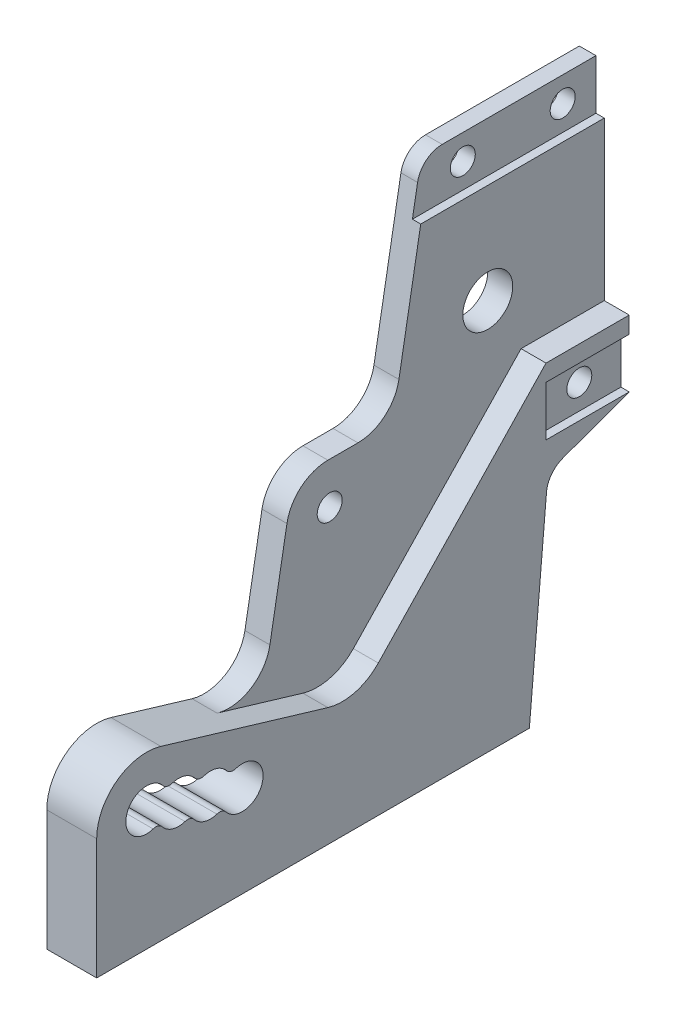
SolidWorks part; units mm, degrees
material "1060 Alloy"
ref_plane "Front Plane" through (0, 0, 0) normal (0, 0, 1) x (1, 0, 0)
ref_plane "Top Plane" through (0, 0, 0) normal (0, 1, 0) x (1, 0, 0)
ref_plane "Right Plane" through (0, 0, 0) normal (1, 0, 0) x (0, 0, -1)
sketch "Sketch1" plane through (0, 0, 0) normal (1, 0, 0) x (0, 0, -1)
  line L1 (0, 0) -> (64, 0)
  line L2 (0, 0) -> (0, 62)
  line L3 (0, 62) -> (64, 62)
  line L4 (64, 0) -> (64, 62)
  circle A0 centre (6, 14.5) radius 2.5
  circle A1 centre (50, 44) radius 3
  dimension "D1" = 6
  dimension "D2" = 5
  dimension "D3" = 14.5
  dimension "D4" = 6
  dimension "D5" = 44
  dimension "D6" = 50
  dimension "D7" = 64
  dimension "D8" = 62
extrude "Boss-Extrude1" add sketch "Sketch1" along normal blind 6
sketch "Sketch3" plane through (6, 0, 0) normal (1, 0, 0) x (0, 0, -1)
  line L57 (64, 0) -> (52, 0)
  line L58 (64, 0) -> (64, 29)
  line L59 (64, 29) -> (54.2259, 25.4425)
  line L60 (52, 0) -> (54.2259, 25.4425)
  dimension "D1" = 70
  dimension "D2" = 29
  dimension "D3" = 52
  dimension "D4" = 85
extrude "Cut-Extrude2" cut sketch "Sketch3" against normal up to next
fillet "Fillet2" radius 3 1 edges at (3, 25.4425, -54.2259)
hole_wizard "Tap Drill for M3 Tap1" positions "Sketch5" profile "Sketch4" hole size "M3" standard "ISO"
sketch "Sketch5" plane through (0, 0, 0) normal (0, -1, 0) x (-1, 0, 0)
  line L0 (0, 0) -> (0, 52) construction
  line L1 (-6, 0) -> (0, 0) construction
  point P0 (-3, 48)
  point P2 (-3, 12)
  dimension "D1" = 3
  dimension "D2" = 12
  dimension "D3" = 36
sketch "Sketch4" plane through (3, 0, -48) normal (1, 0, 0) x (0, 0, -1)
  line L0 (0, 0) -> (0, 9.7511)
  line L1 (0, 9.7511) -> (1.25, 9)
  line L2 (1.25, 9) -> (1.25, 0)
  line L5 (1.25, 0) -> (0, 0)
  line L10 (0, 9.7511) -> (-1.25, 9) construction
  line L11 (0, -6.35) -> (0, 107.95) construction
  dimension "Hole Dia." = 2.5
  dimension "Hole Depth" = 9
  dimension "Drill Angle" = 118
sketch "Sketch9" plane through (6, 0, 0) normal (1, 0, 0) x (0, 0, -1)
  line L0 (7.7183, 20.2487) -> (27.7834, 14.2513)
  line L1 (0, 0) -> (52, 0) construction
  line L19 (43, 62) -> (35.4106, 18.9581)
  line L21 (0, 62) -> (0, 0) construction
  line L22 (43, 62) -> (0, 62)
  line L23 (0, 62) -> (0, 14.5)
  line L24 (0, 62) -> (0, 0) construction
  line L25 (64, 62) -> (0, 62) construction
  arc A0 (35.4106, 18.9581) -> (27.7834, 14.2513) centre (29.5017, 20) cw
  arc A12 (0, 14.5) -> (7.7183, 20.2487) centre (6, 14.5) cw
  circle A16 centre (6, 14.5) radius 2.5 construction
  dimension "D1" = 43
  dimension "D2" = 80
  dimension "D3" = 20
extrude "Cut-Extrude3" cut sketch "Sketch9" against normal blind 8
sketch "Sketch13" plane through (6, 0, 0) normal (1, 0, 0) x (0, 0, -1)
  line L0 (64, 29) -> (64, 62) construction
  line L1 (54, 37) -> (64, 37)
  line L2 (64, 62) -> (43, 62) construction
  line L3 (64, 62) -> (42, 62)
  line L4 (64, 37) -> (64, 62)
  line L11 (42, 62) -> (33.8443, 15.8597)
  line L15 (33.8443, 15.8597) -> (54, 37)
  arc A0 (27.7834, 14.2513) -> (35.4106, 18.9581) centre (29.5017, 20) ccw construction
  dimension "D1" = 10
  dimension "D3" = 25
  dimension "D4" = 22
extrude "Cut-Extrude4" cut sketch "Sketch13" against normal blind 3
fillet "Fillet3" radius 3 1 edges at (1.5, 62, -43)
sketch "Sketch14" plane through (3, 0, 0) normal (1, 0, 0) x (0, 0, -1)
  line L0 (64, 37) -> (64, 62) construction
  line L1 (64, 62) -> (45.5173, 62) construction
  circle A0 centre (60, 59) radius 1.5
  circle A1 centre (48, 59) radius 1.5
  dimension "D1" = 3
  dimension "D2" = 12
  dimension "D3" = 4
  dimension "D4" = 3
extrude "Cut-Extrude5" cut sketch "Sketch14" against normal up to next
sketch "Sketch15" plane through (0, 0, 0) normal (-1, 0, 0) x (0, 0, 1)
  line L0 (-6, 14.5) -> (-26.0652, 8.5026) construction
  line L1 (-27.7834, 14.2513) -> (-7.7183, 20.2487) construction
  circle A0 centre (-9.8325, 13.3545) radius 2.5
  circle A1 centre (-6, 14.5) radius 2.5 construction
  dimension "D1" = 4
extrude "Cut-Extrude6" cut sketch "Sketch15" against normal up to next
pattern_linear "LPattern3" count 3 spacing 4 along (0, -0.2864, -0.9581) of "Cut-Extrude6"
fillet "Fillet4" radius 1 6 edges at (3, 12.4901, -7.4867) (3, 11.3446, -11.3191) (3, 10.1991, -15.1516) (3, 13.0734, -16.0107) (3, 14.2189, -12.1783) (3, 15.3644, -8.3458)
sketch "Sketch16" plane through (3, 0, 0) normal (1, 0, 0) x (0, 0, -1)
  line L0 (42.5629, 59.5209) -> (35.4106, 18.9581) construction
  line L1 (64, 62) -> (41.942, 62)
  line L2 (64, 62) -> (64, 56)
  line L3 (64, 56) -> (41.942, 56)
  line L4 (41.942, 62) -> (41.942, 56)
  dimension "D1" = 6
extrude "Cut-Extrude7" cut sketch "Sketch16" against normal blind 1
sketch "Sketch17" plane through (6, 0, 0) normal (1, 0, 0) x (0, 0, -1)
  line L0 (64, 29) -> (64, 37) construction
  line L1 (64, 29) -> (54, 29)
  line L2 (64, 29) -> (64, 35)
  line L3 (64, 35) -> (54, 35)
  line L4 (54, 29) -> (54, 35)
  line L5 (64, 29) -> (56.0219, 26.0962) construction
  dimension "D1" = 10
  dimension "D2" = 6
extrude "Cut-Extrude8" cut sketch "Sketch17" against normal blind 1
sketch "Sketch18" plane through (0, 0, 0) normal (-1, 0, 0) x (0, 0, 1)
  line L0 (-38.5918, 37) -> (-26.5918, 37)
  line L1 (-42.5629, 59.5209) -> (-35.4106, 18.9581) construction
  line L2 (-26.5918, 37) -> (-22.8411, 15.7285)
  line L3 (-27.7834, 14.2513) -> (-7.7183, 20.2487) construction
  line L4 (-22.8411, 15.7285) -> (-34.2403, 12.3214)
  line L5 (-34.2403, 12.3214) -> (-38.5918, 37)
  line L6 (-64, 62) -> (-45.5173, 62) construction
  line L7 (0, 0) -> (-52, 0) construction
  line L8 (0, 14.5) -> (0, 0) construction
  circle A0 centre (-31, 32) radius 1.5
  dimension "D5" = 3
  dimension "D1" = 25
  dimension "D2" = 12
  dimension "D3" = 32
  dimension "D4" = 31
extrude "Boss-Extrude2" add sketch "Sketch18" against normal up to surface (3 mm away) up to face at (3, 36.7837, -48.9043)
fillet "Fillet5" radius 5 3 edges at (1.5, 15.7285, -22.8411) (1.5, 37, -26.5918) (1.5, 37, -38.5918)
sketch "Sketch19" plane through (5, 0, 0) normal (1, 0, 0) x (0, 0, -1)
  line L0 (54, 35) -> (54, 29) construction
  line L1 (54, 29) -> (64, 29) construction
  circle A0 centre (59, 32) radius 1.5
  dimension "D3" = 3
  dimension "D1" = 5
  dimension "D2" = 3
extrude "Cut-Extrude9" cut sketch "Sketch19" against normal up to next
chamfer "Chamfer1" distance 1.5 angle 45 1 edges at (0, 32, -57.5)
